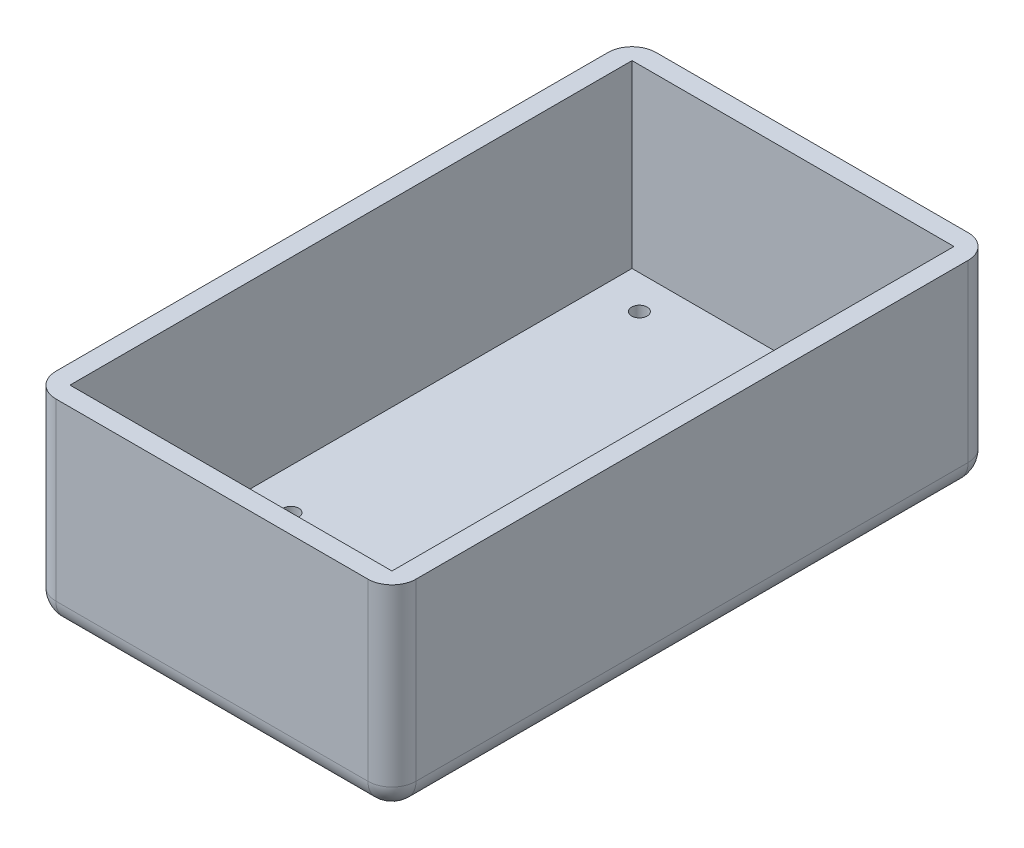
SolidWorks part; units mm, degrees
ref_plane "Front Plane" through (0, 0, 0) normal (0, 0, 1) x (1, 0, 0)
ref_plane "Top Plane" through (0, 0, 0) normal (0, 1, 0) x (1, 0, 0)
ref_plane "Right Plane" through (0, 0, 0) normal (1, 0, 0) x (0, 0, -1)
sketch "Sketch1" plane through (0, 0, 0) normal (0, 1, 0) x (1, 0, 0)
  line L1 (-30, 50) -> (30, 50)
  line L2 (-30, 50) -> (-30, -50)
  line L3 (-30, -50) -> (30, -50)
  line L4 (30, 50) -> (30, -50)
  line L5 (-30, 50) -> (30, -50) construction
  line L6 (-30, -50) -> (30, 50) construction
  line L7 (-26.825, 46.825) -> (26.825, 46.825)
  line L8 (-26.825, 46.825) -> (-26.825, -46.825)
  line L9 (-26.825, -46.825) -> (26.825, -46.825)
  line L10 (26.825, 46.825) -> (26.825, -46.825)
  line L11 (-26.825, 46.825) -> (26.825, -46.825) construction
  line L12 (-26.825, -46.825) -> (26.825, 46.825) construction
  point P0 (0, 0)
  point P6 (0, 0)
  dimension "D1" = 3.175
  dimension "D2" = 3.175
  dimension "D3" = 100
  dimension "D4" = 60
extrude "Boss-Extrude1" add sketch "Sketch1" along normal blind 30
sketch "Sketch2" plane through (0, 0, 0) normal (0, -1, 0) x (1, 0, 0)
  line L1 (30, -50) -> (-30, -50)
  line L2 (30, -50) -> (30, 50)
  line L3 (30, 50) -> (-30, 50)
  line L4 (-30, -50) -> (-30, 50)
extrude "Boss-Extrude2" add sketch "Sketch2" along normal blind 3.175
fillet "Fillet1" radius 4 8 edges at (30, 13.4125, 50) (30, 13.4125, -50) (-30, 13.4125, -50) (-30, 13.4125, 50) (0, -3.175, 50) (-30, -3.175, 0) (0, -3.175, -50) (30, -3.175, 0)
sketch "Sketch3" plane through (0, 0, 0) normal (0, 1, 0) x (1, 0, 0)
  line L0 (-26.825, -46.825) -> (26.825, -46.825) construction
  line L1 (-20, 41.225) -> (3.05, 41.225) construction
  line L2 (-20, 41.225) -> (-20, -16.825) construction
  line L3 (-20, -16.825) -> (3.05, -16.825) construction
  line L4 (3.05, 41.225) -> (3.05, -16.825) construction
  line L6 (-26, -46) -> (-26, 46) construction
  circle A0 centre (-20, 41.225) radius 1.3
  circle A1 centre (3.05, 41.225) radius 1.3
  circle A2 centre (3.05, -16.825) radius 1.3
  circle A3 centre (-20, -16.825) radius 1.3
  dimension "D2" = 2.6
  dimension "D1" = 58.05
  dimension "D3" = 23.05
  dimension "D4" = 30
  dimension "D5" = 6
extrude "Cut-Extrude1" cut sketch "Sketch3" against normal up to surface (3.175 mm away) up to face at (0, -3.175, 0)
